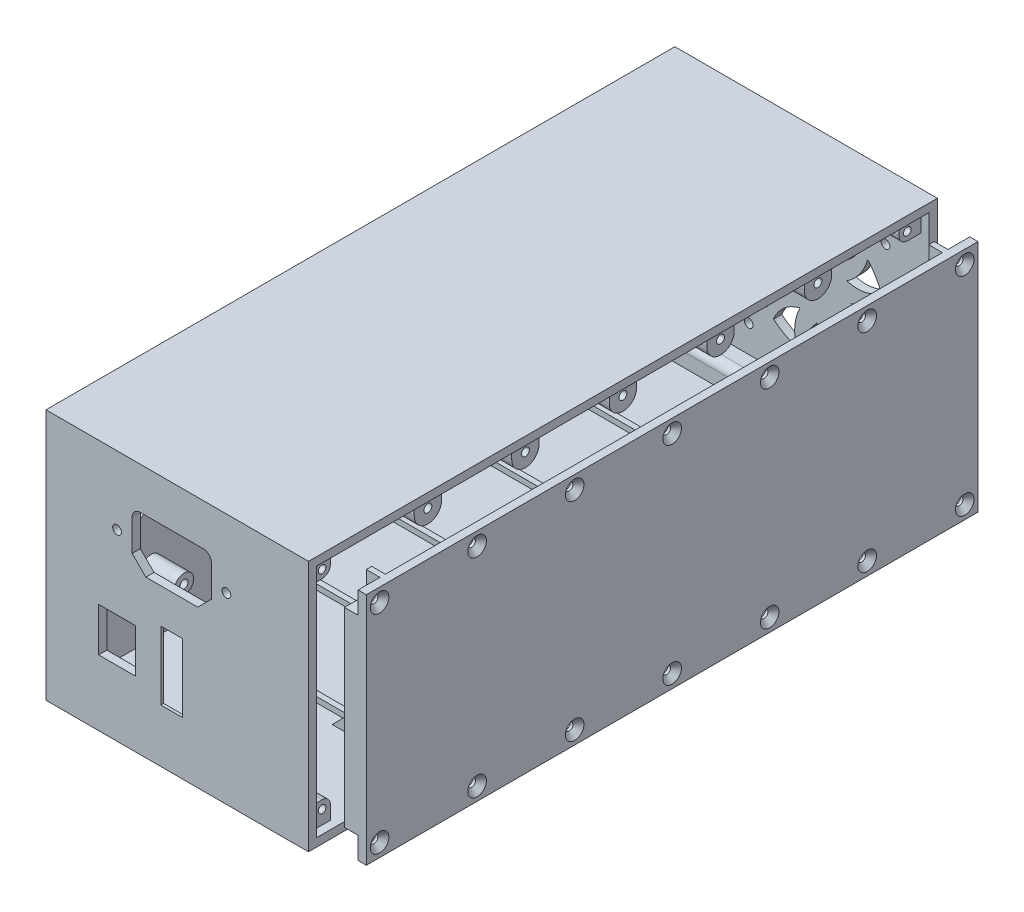
SolidWorks part; units mm, degrees
ref_plane "Front Plane" through (0, 0, 0) normal (0, 0, 1) x (1, 0, 0)
ref_plane "Top Plane" through (0, 0, 0) normal (0, 1, 0) x (1, 0, 0)
ref_plane "Right Plane" through (0, 0, 0) normal (1, 0, 0) x (0, 0, -1)
sketch "Sketch1" plane through (0, 0, 0) normal (1, 0, 0) x (0, 0, -1)
  line L1 (115, 46) -> (-115, 46)
  line L2 (115, 46) -> (115, -46)
  line L3 (115, -46) -> (-115, -46)
  line L4 (-115, 46) -> (-115, -46)
  line L5 (115, 46) -> (-115, -46) construction
  line L6 (115, -46) -> (-115, 46) construction
  point P0 (0, 0)
  dimension "D1" = 92
  dimension "D2" = 230
extrude "Boss-Extrude1" add sketch "Sketch1" along normal blind 3
sketch "Sketch2" plane through (3, 0, 0) normal (1, 0, 0) x (0, 0, -1)
  line L0 (-112, 43) -> (-112, -43)
  line L1 (-112, -43) -> (112, -43)
  line L2 (112, -43) -> (112, 43)
  line L3 (112, 43) -> (-112, 43)
  line L4 (-115, 46) -> (-115, -46)
  line L5 (-115, -46) -> (115, -46)
  line L6 (115, -46) -> (115, 46)
  line L7 (115, 46) -> (-115, 46)
  line L8 (-115, 46) -> (-115, -46)
  line L9 (-115, -46) -> (115, -46)
  line L10 (115, -46) -> (115, 46)
  line L11 (115, 46) -> (-115, 46)
  dimension "D1" = 0
  dimension "D2" = 3
extrude "Boss-Extrude2" add sketch "Sketch2" along normal blind 93
sketch "Sketch3" plane through (0, 0, 0) normal (-1, 0, 0) x (0, 0, 1)
  line L0 (-115, 0) -> (115, 0) construction
  line L1 (-115, -46) -> (-115, 46) construction
  line L2 (115, 46) -> (115, -46) construction
  line L3 (0, 46) -> (0, -46) construction
  line L4 (-115, 46) -> (115, 46) construction
  line L5 (115, -46) -> (-115, -46) construction
  line L6 (26.5, -7.75) -> (18.5, -7.75)
  line L7 (11.5, 7.75) -> (3.5, 7.75)
  line L8 (11.5, 7.75) -> (11.5, -7.75)
  line L9 (11.5, -7.75) -> (3.5, -7.75)
  line L10 (3.5, 7.75) -> (3.5, -7.75)
  line L11 (11.5, 7.75) -> (3.5, -7.75) construction
  line L12 (11.5, -7.75) -> (3.5, 7.75) construction
  line L13 (26.5, 7.75) -> (26.5, -7.75)
  line L14 (26.5, 7.75) -> (18.5, 7.75)
  line L15 (18.5, 7.75) -> (18.5, -7.75)
  line L16 (41.5, -7.75) -> (33.5, -7.75)
  line L17 (41.5, 7.75) -> (41.5, -7.75)
  line L18 (41.5, 7.75) -> (33.5, 7.75)
  line L19 (33.5, 7.75) -> (33.5, -7.75)
  line L20 (56.5, -7.75) -> (48.5, -7.75)
  line L21 (56.5, 7.75) -> (56.5, -7.75)
  line L22 (56.5, 7.75) -> (48.5, 7.75)
  line L23 (48.5, 7.75) -> (48.5, -7.75)
  line L24 (71.5, -7.75) -> (63.5, -7.75)
  line L25 (71.5, 7.75) -> (71.5, -7.75)
  line L26 (71.5, 7.75) -> (63.5, 7.75)
  line L27 (63.5, 7.75) -> (63.5, -7.75)
  line L28 (11.5, -7.75) -> (3.5, -7.75)
  line L29 (11.5, 7.75) -> (11.5, -7.75)
  line L30 (11.5, 7.75) -> (3.5, 7.75)
  line L31 (3.5, 7.75) -> (3.5, -7.75)
  line L32 (26.5, -7.75) -> (18.5, -7.75)
  line L33 (26.5, 7.75) -> (26.5, -7.75)
  line L34 (26.5, 7.75) -> (18.5, 7.75)
  line L35 (18.5, 7.75) -> (18.5, -7.75)
  line L36 (41.5, -7.75) -> (33.5, -7.75)
  line L37 (41.5, 7.75) -> (41.5, -7.75)
  line L38 (41.5, 7.75) -> (33.5, 7.75)
  line L39 (33.5, 7.75) -> (33.5, -7.75)
  line L40 (56.5, -7.75) -> (48.5, -7.75)
  line L41 (56.5, 7.75) -> (56.5, -7.75)
  line L42 (56.5, 7.75) -> (48.5, 7.75)
  line L43 (48.5, 7.75) -> (48.5, -7.75)
  line L44 (-3.5, -7.75) -> (-11.5, -7.75)
  line L45 (-3.5, 7.75) -> (-3.5, -7.75)
  line L46 (-3.5, 7.75) -> (-11.5, 7.75)
  line L47 (-11.5, 7.75) -> (-11.5, -7.75)
  line L48 (11.5, -7.75) -> (3.5, -7.75)
  line L49 (11.5, 7.75) -> (11.5, -7.75)
  line L50 (11.5, 7.75) -> (3.5, 7.75)
  line L51 (3.5, 7.75) -> (3.5, -7.75)
  line L52 (26.5, -7.75) -> (18.5, -7.75)
  line L53 (26.5, 7.75) -> (26.5, -7.75)
  line L54 (26.5, 7.75) -> (18.5, 7.75)
  line L55 (18.5, 7.75) -> (18.5, -7.75)
  line L56 (41.5, -7.75) -> (33.5, -7.75)
  line L57 (41.5, 7.75) -> (41.5, -7.75)
  line L58 (41.5, 7.75) -> (33.5, 7.75)
  line L59 (33.5, 7.75) -> (33.5, -7.75)
  line L60 (-18.5, -7.75) -> (-26.5, -7.75)
  line L61 (-18.5, 7.75) -> (-18.5, -7.75)
  line L62 (-18.5, 7.75) -> (-26.5, 7.75)
  line L63 (-26.5, 7.75) -> (-26.5, -7.75)
  line L64 (-3.5, -7.75) -> (-11.5, -7.75)
  line L65 (-3.5, 7.75) -> (-3.5, -7.75)
  line L66 (-3.5, 7.75) -> (-11.5, 7.75)
  line L67 (-11.5, 7.75) -> (-11.5, -7.75)
  line L68 (11.5, -7.75) -> (3.5, -7.75)
  line L69 (11.5, 7.75) -> (11.5, -7.75)
  line L70 (11.5, 7.75) -> (3.5, 7.75)
  line L71 (3.5, 7.75) -> (3.5, -7.75)
  line L72 (26.5, -7.75) -> (18.5, -7.75)
  line L73 (26.5, 7.75) -> (26.5, -7.75)
  line L74 (26.5, 7.75) -> (18.5, 7.75)
  line L75 (18.5, 7.75) -> (18.5, -7.75)
  line L76 (-33.5, -7.75) -> (-41.5, -7.75)
  line L77 (-33.5, 7.75) -> (-33.5, -7.75)
  line L78 (-33.5, 7.75) -> (-41.5, 7.75)
  line L79 (-41.5, 7.75) -> (-41.5, -7.75)
  line L80 (-18.5, -7.75) -> (-26.5, -7.75)
  line L81 (-18.5, 7.75) -> (-18.5, -7.75)
  line L82 (-18.5, 7.75) -> (-26.5, 7.75)
  line L83 (-26.5, 7.75) -> (-26.5, -7.75)
  line L84 (-3.5, -7.75) -> (-11.5, -7.75)
  line L85 (-3.5, 7.75) -> (-3.5, -7.75)
  line L86 (-3.5, 7.75) -> (-11.5, 7.75)
  line L87 (-11.5, 7.75) -> (-11.5, -7.75)
  line L88 (11.5, -7.75) -> (3.5, -7.75)
  line L89 (11.5, 7.75) -> (11.5, -7.75)
  line L90 (11.5, 7.75) -> (3.5, 7.75)
  line L91 (3.5, 7.75) -> (3.5, -7.75)
  line L92 (-48.5, -7.75) -> (-56.5, -7.75)
  line L93 (-48.5, 7.75) -> (-48.5, -7.75)
  line L94 (-48.5, 7.75) -> (-56.5, 7.75)
  line L95 (-56.5, 7.75) -> (-56.5, -7.75)
  line L96 (-33.5, -7.75) -> (-41.5, -7.75)
  line L97 (-33.5, 7.75) -> (-33.5, -7.75)
  line L98 (-33.5, 7.75) -> (-41.5, 7.75)
  line L99 (-41.5, 7.75) -> (-41.5, -7.75)
  line L100 (-18.5, -7.75) -> (-26.5, -7.75)
  line L101 (-18.5, 7.75) -> (-18.5, -7.75)
  line L102 (-18.5, 7.75) -> (-26.5, 7.75)
  line L103 (-26.5, 7.75) -> (-26.5, -7.75)
  line L104 (-3.5, -7.75) -> (-11.5, -7.75)
  line L105 (-3.5, 7.75) -> (-3.5, -7.75)
  line L106 (-3.5, 7.75) -> (-11.5, 7.75)
  line L107 (-11.5, 7.75) -> (-11.5, -7.75)
  line L108 (-3.5, -7.75) -> (-11.5, -7.75)
  line L109 (-3.5, 7.75) -> (-3.5, -7.75)
  line L110 (-3.5, 7.75) -> (-11.5, 7.75)
  line L111 (-11.5, 7.75) -> (-11.5, -7.75)
  line L112 (-18.5, -7.75) -> (-26.5, -7.75)
  line L113 (-18.5, 7.75) -> (-18.5, -7.75)
  line L114 (-18.5, 7.75) -> (-26.5, 7.75)
  line L115 (-26.5, 7.75) -> (-26.5, -7.75)
  line L116 (-33.5, -7.75) -> (-41.5, -7.75)
  line L117 (-33.5, 7.75) -> (-33.5, -7.75)
  line L118 (-33.5, 7.75) -> (-41.5, 7.75)
  line L119 (-41.5, 7.75) -> (-41.5, -7.75)
  line L120 (-48.5, -7.75) -> (-56.5, -7.75)
  line L121 (-48.5, 7.75) -> (-48.5, -7.75)
  line L122 (-48.5, 7.75) -> (-56.5, 7.75)
  line L123 (-56.5, 7.75) -> (-56.5, -7.75)
  line L124 (-63.5, -7.75) -> (-71.5, -7.75)
  line L125 (-63.5, 7.75) -> (-63.5, -7.75)
  line L126 (-63.5, 7.75) -> (-71.5, 7.75)
  line L127 (-71.5, 7.75) -> (-71.5, -7.75)
  circle A0 centre (84.6037, 0) radius 1
  point P12 (7.5, 0)
  dimension "D6" = 2
  dimension "D1" = 7.5
  dimension "D2" = 15.5
  dimension "D3" = 8
  dimension "D4" = 5
  dimension "D5" = 6
extrude "Cut-Extrude1" cut sketch "Sketch3" against normal up to surface (3 mm away) contours L126 L127 L124 L125 | L94 L95 L92 L93 | L78 L79 L76 L77 | L62 L63 L60 L61 | L46 L47 L44 L45 | L7 L10 L9 L8 | L14 L15 L6 L13 | L18 L19 L16 L17 | L22 L23 L20 L21 | L26 L27 L24 L25 | A0 region at (0, 0, 22.5) region at (0, 0, 7.5) region at (0, 0, 37.5) region at (0, 0, 52.5) region at (0, 0, 67.5) region at (0, 0, -7.5) region at (0, 0, -22.5) region at (0, 0, -37.5) region at (0, 0, -52.5) region at (0, 0, -67.5) region at (0, 0, 84.6037) up to face at (3, 0, 0)
sketch "Sketch4" plane through (96, 0, 0) normal (1, 0, 0) x (0, 0, -1)
  line L0 (0, 43) -> (0, -43) construction
  line L1 (112, 43) -> (-112, 43) construction
  line L2 (-112, -43) -> (112, -43) construction
  line L3 (-112, 43) -> (-112, -43) construction
  line L4 (-104, 38) -> (-104, 43)
  line L5 (-104, 43) -> (-112, 43)
  line L6 (-112, 43) -> (-112, 35)
  line L7 (-112, 35) -> (-107, 35)
  line L8 (0, 0) -> (-112, 0) construction
  line L9 (-107, -35) -> (-112, -35)
  line L10 (-112, 43) -> (-112, -43) construction
  line L11 (-112, -35) -> (-112, -43)
  line L12 (-104, -38) -> (-104, -43)
  line L13 (-104, -43) -> (-112, -43)
  line L14 (104, -43) -> (112, -43)
  line L15 (112, -35) -> (112, -43)
  line L16 (107, -35) -> (112, -35)
  line L17 (112, 35) -> (107, 35)
  line L18 (112, 43) -> (112, 35)
  line L19 (104, 43) -> (112, 43)
  line L20 (104, 38) -> (104, 43)
  line L21 (104, -38) -> (104, -43)
  circle A0 centre (-107, 38) radius 1.4
  circle A1 centre (-107, -38) radius 1.4
  arc A2 (-104, 38) -> (-107, 35) centre (-107, 38) cw
  arc A3 (-107, -35) -> (-104, -38) centre (-107, -38) cw
  arc A4 (107, -35) -> (104, -38) centre (107, -38) ccw
  circle A5 centre (107, -38) radius 1.4
  arc A6 (104, 38) -> (107, 35) centre (107, 38) ccw
  circle A7 centre (107, 38) radius 1.4
  dimension "D5" = 2.8
  dimension "D6" = 3
  dimension "D1" = 5
  dimension "D2" = 5
  dimension "D3" = 5
  dimension "D4" = 5
extrude "Boss-Extrude3" add sketch "Sketch4" against normal up to surface (93 mm away) from offset 3 up to face at (3, 0, -67.5) offset against normal yes
sketch "Sketch5" plane through (93, 0, 0) normal (1, 0, 0) x (0, 0, -1)
  circle A0 centre (-107, -38) radius 1.4 construction
  circle A1 centre (107, -38) radius 1.4 construction
  circle A2 centre (107, 38) radius 1.4 construction
  circle A3 centre (-107, 38) radius 1.4 construction
  circle A4 centre (-107, -38) radius 1.4
  circle A5 centre (107, -38) radius 1.4
  circle A6 centre (107, 38) radius 1.4
  circle A7 centre (-107, 38) radius 1.4
extrude "Boss-Extrude4" add sketch "Sketch5" against normal up to surface (90 mm away) from offset 20 up to face at (3, 0, -67.5) offset against normal yes
sketch "Sketch6" plane through (0, 0, 115) normal (0, 0, 1) x (1, 0, 0)
  line L0 (46, 46) -> (46, -46) construction
  line L1 (96, 46) -> (0, 46) construction
  line L2 (96, -46) -> (0, -46) construction
  line L3 (93, 43) -> (93, 38) construction
  line L4 (79.2275, 21) -> (12.7725, 21) construction
  line L5 (36.5, 11.25) -> (31.5, 16.25)
  line L6 (57.5, 30.75) -> (34.5, 30.75)
  line L7 (60.5, 27.75) -> (60.5, 16.25)
  line L8 (55.5, 11.25) -> (36.5, 11.25)
  line L9 (31.5, 27.75) -> (31.5, 16.25)
  line L10 (60.5, 30.75) -> (31.5, 11.25) construction
  line L11 (60.5, 11.25) -> (31.5, 30.75) construction
  line L12 (60.5, 16.25) -> (55.5, 11.25)
  line L14 (50, -1.5) -> (42, -1.5)
  line L15 (50, -1.5) -> (50, -26.5)
  line L16 (50, -26.5) -> (42, -26.5)
  line L17 (42, -1.5) -> (42, -26.5)
  line L18 (50, -1.5) -> (42, -26.5) construction
  line L19 (50, -26.5) -> (42, -1.5) construction
  line L20 (32.75, -6) -> (19.25, -6)
  line L21 (32.75, -6) -> (32.75, -22)
  line L22 (32.75, -22) -> (19.25, -22)
  line L23 (19.25, -6) -> (19.25, -22)
  line L24 (32.75, -6) -> (19.25, -22) construction
  line L25 (32.75, -22) -> (19.25, -6) construction
  circle A2 centre (26, 21) radius 1.6
  circle A3 centre (66, 21) radius 1.6
  arc A4 (57.5, 30.75) -> (60.5, 27.75) centre (57.5, 27.75) cw
  arc A5 (34.5, 30.75) -> (31.5, 27.75) centre (34.5, 27.75) ccw
  point P11 (46, 21)
  point P15 (46, 21)
  point P30 (46, -14)
  point P35 (26, -14)
  dimension "D2" = 3.2
  dimension "D7" = 3
  dimension "D1" = 47
  dimension "D3" = 20
  dimension "D4" = 20
  dimension "D5" = 29
  dimension "D6" = 19.5
  dimension "D8" = 25
  dimension "D9" = 8
  dimension "D10" = 25
  dimension "D13" = 32
  dimension "D14" = 20
  dimension "D15" = 13.5
  dimension "D16" = 16
extrude "Cut-Extrude2" cut sketch "Sketch6" against normal up to surface (3 mm away) up to face at (71.25, 0, 112)
sketch "Sketch7" plane through (0, 0, 112) normal (0, 0, -1) x (-1, 0, 0)
  line L0 (-39.5, 6) -> (-39.5, -32.5)
  line L1 (-39.5, -32.5) -> (-52, -32.5)
  line L2 (-52, -32.5) -> (-52, 6)
  line L3 (-52, 6) -> (-39.5, 6)
  line L4 (-50, -1.5) -> (-42, -1.5) construction
  line L5 (-50, -26.5) -> (-50, -1.5) construction
  dimension "D1" = 7.5
  dimension "D2" = 2
  dimension "D3" = 38.5
  dimension "D4" = 12.5
extrude "Cut-Extrude3" cut sketch "Sketch7" against normal blind 2
chamfer "Chamfer1" distance 2 angle 45 1 edges at (52, -13.25, 112)
sketch "Sketch8" plane through (3, 0, 0) normal (1, 0, 0) x (0, 0, -1)
  line L0 (-71.5, 0) -> (91.1958, 0) construction
  line L1 (-71.5, -7.75) -> (-71.5, 7.75) construction
  line L2 (-79.5, 43) -> (-79.5, -43) construction
  line L3 (112, 43) -> (-112, 43) construction
  line L4 (-104, -43) -> (104, -43) construction
  circle A0 centre (-79.5, 19.5) radius 1.5
  circle A1 centre (-79.5, -19.5) radius 1.5
  circle A2 centre (-79.5, 19.5) radius 3.5
  circle A3 centre (-79.5, -19.5) radius 3.5
  circle A4 centre (72, -19.5) radius 1.5
  circle A5 centre (72, -19.5) radius 3.5
  circle A6 centre (72, 19.5) radius 3.5
  circle A7 centre (72, 19.5) radius 1.5
  dimension "D1" = 3
  dimension "D2" = 7
  dimension "D3" = 8
  dimension "D5" = 19.5
  dimension "D6" = 19.5
  dimension "D7" = 19.5
  dimension "D8" = 19.5
  dimension "D9" = 151.5
extrude "Boss-Extrude5" add sketch "Sketch8" along normal blind 12
sketch "Sketch9" plane through (3, 0, 0) normal (1, 0, 0) x (0, 0, -1)
  circle A0 centre (-84.6037, 0) radius 3
extrude "Cut-Extrude4" cut sketch "Sketch9" against normal blind 2.2
ref_plane "Plane1" through (106, 0, 0) normal (1, 0, 0) x (0, 0, -1)
sketch "Sketch10" plane through (106, 0, 0) normal (1, 0, 0) x (0, 0, -1)
  line L112 (107, -32.85) -> (109.85, -32.85)
  line L113 (109.85, -32.85) -> (109.85, 32.85)
  line L114 (109.85, 32.85) -> (107, 32.85)
  line L115 (101.85, 38) -> (101.85, 40.85)
  line L116 (101.85, 40.85) -> (-101.85, 40.85)
  line L117 (-101.85, 40.85) -> (-101.85, 38)
  line L118 (-107, 32.85) -> (-109.85, 32.85)
  line L119 (-109.85, 32.85) -> (-109.85, -32.85)
  line L120 (-109.85, -32.85) -> (-107, -32.85)
  line L121 (-101.85, -38) -> (-101.85, -40.85)
  line L122 (-101.85, -40.85) -> (101.85, -40.85)
  line L123 (101.85, -40.85) -> (101.85, -38)
  line L124 (107, -34.85) -> (111.85, -34.85)
  line L125 (103.85, -42.85) -> (103.85, -38)
  line L126 (-103.85, -42.85) -> (103.85, -42.85)
  line L127 (-103.85, -38) -> (-103.85, -42.85)
  line L128 (-111.85, -34.85) -> (-107, -34.85)
  line L129 (-111.85, 34.85) -> (-111.85, -34.85)
  line L130 (-107, 34.85) -> (-111.85, 34.85)
  line L131 (-103.85, 42.85) -> (-103.85, 38)
  line L132 (103.85, 42.85) -> (-103.85, 42.85)
  line L133 (103.85, 38) -> (103.85, 42.85)
  line L134 (111.85, 34.85) -> (107, 34.85)
  line L135 (111.85, -34.85) -> (111.85, 34.85)
  line L136 (107, -34.85) -> (111.85, -34.85)
  line L137 (103.85, -42.85) -> (103.85, -38)
  line L138 (-103.85, -42.85) -> (103.85, -42.85)
  line L139 (-103.85, -38) -> (-103.85, -42.85)
  line L140 (-111.85, -34.85) -> (-107, -34.85)
  line L141 (-111.85, 34.85) -> (-111.85, -34.85)
  line L142 (-107, 34.85) -> (-111.85, 34.85)
  line L143 (-103.85, 42.85) -> (-103.85, 38)
  line L144 (103.85, 42.85) -> (-103.85, 42.85)
  line L145 (103.85, 38) -> (103.85, 42.85)
  line L146 (111.85, 34.85) -> (107, 34.85)
  line L147 (111.85, -34.85) -> (111.85, 34.85)
  arc A36 (107, -34.85) -> (103.85, -38) centre (107, -38) ccw
  arc A37 (-103.85, -38) -> (-107, -34.85) centre (-107, -38) ccw
  arc A38 (-107, 34.85) -> (-103.85, 38) centre (-107, 38) ccw
  arc A39 (103.85, 38) -> (107, 34.85) centre (107, 38) ccw
  arc A40 (107, -34.85) -> (103.85, -38) centre (107, -38) ccw
  arc A41 (-103.85, -38) -> (-107, -34.85) centre (-107, -38) ccw
  arc A42 (-107, 34.85) -> (-103.85, 38) centre (-107, 38) ccw
  arc A43 (103.85, 38) -> (107, 34.85) centre (107, 38) ccw
  arc A48 (101.85, 38) -> (107, 32.85) centre (107, 38) ccw
  arc A49 (-107, 32.85) -> (-101.85, 38) centre (-107, 38) ccw
  arc A50 (-101.85, -38) -> (-107, -32.85) centre (-107, -38) ccw
  arc A51 (107, -32.85) -> (101.85, -38) centre (107, -38) ccw
  dimension "D1" = 0.15
  dimension "D2" = 2
extrude "Boss-Extrude6" add sketch "Sketch10" along normal blind 5 separate body
sketch "Sketch11" plane through (111, 0, 0) normal (1, 0, 0) x (0, 0, -1)
  line L0 (111.85, -34.85) -> (111.85, 34.85) construction
  line L1 (-103.85, -42.85) -> (103.85, -42.85) construction
  line L2 (-111.85, 34.85) -> (-111.85, -34.85) construction
  line L3 (103.85, 42.85) -> (-103.85, 42.85) construction
  line L4 (111.85, -34.85) -> (111.85, 34.85)
  line L5 (-103.85, -42.85) -> (103.85, -42.85)
  line L6 (-111.85, 34.85) -> (-111.85, -34.85)
  line L7 (103.85, 42.85) -> (-103.85, 42.85)
  line L8 (103.85, 42.85) -> (111.85, 42.85)
  line L9 (111.85, 42.85) -> (111.85, 34.85)
  line L10 (111.85, -34.85) -> (111.85, -42.85)
  line L11 (111.85, -42.85) -> (103.85, -42.85)
  line L12 (-111.85, -34.85) -> (-111.85, -42.85)
  line L13 (-111.85, -42.85) -> (-103.85, -42.85)
  line L14 (-103.85, 42.85) -> (-111.85, 42.85)
  line L15 (-111.85, 42.85) -> (-111.85, 34.85)
  circle A0 centre (-107, -38) radius 1.4 construction
  circle A1 centre (107, -38) radius 1.4 construction
  circle A2 centre (107, 38) radius 1.4 construction
  circle A3 centre (-107, 38) radius 1.4 construction
  circle A4 centre (-107, -38) radius 1.4
  circle A5 centre (107, -38) radius 1.4
  circle A6 centre (107, 38) radius 1.4
  circle A7 centre (-107, 38) radius 1.4
extrude "Boss-Extrude7" add sketch "Sketch11" along normal blind 3
sketch "Sketch12" plane through (114, 0, 0) normal (1, 0, 0) x (0, 0, -1)
  line L0 (-112, 0) -> (111.85, 0) construction
  line L1 (89, 29.25) -> (-89, 29.25) construction
  line L2 (89, 29.25) -> (89, -29.25) construction
  line L3 (89, -29.25) -> (-89, -29.25) construction
  line L4 (-89, 29.25) -> (-89, -29.25) construction
  line L5 (89, 29.25) -> (-89, -29.25) construction
  line L6 (89, -29.25) -> (-89, 29.25) construction
  line L7 (-112, 43) -> (-112, -43) construction
  line L8 (111.85, -42.85) -> (111.85, 42.85) construction
  circle A0 centre (-89, 29.25) radius 1.8
  circle A1 centre (-89, -29.25) radius 1.8
  circle A2 centre (89, -29.25) radius 1.8
  circle A3 centre (89, 29.25) radius 1.8
  circle A4 centre (-47.3819, 9) radius 1.8
  circle A5 centre (26.6181, 9) radius 1.8
  circle A6 centre (-4.3819, 9) radius 1.8
  circle A7 centre (-4.3819, -9) radius 1.8
  point P0 (0, 0)
  dimension "D3" = 3.6
  dimension "D10" = 3.6
  dimension "D1" = 58.5
  dimension "D2" = 178
  dimension "D4" = 9
  dimension "D5" = 9
  dimension "D6" = 74
  dimension "D7" = 31
  dimension "D8" = 9
  dimension "D9" = 9
sketch "Sketch13" plane through (96, 0, 0) normal (1, 0, 0) x (0, 0, -1)
  line L12 (104, 38) -> (104, 43)
  line L13 (104, 43) -> (-104, 43)
  line L14 (-104, 43) -> (-104, 38)
  line L15 (-107, 35) -> (-112, 35)
  line L16 (-112, 35) -> (-112, -35)
  line L17 (-112, -35) -> (-107, -35)
  line L18 (-104, -38) -> (-104, -43)
  line L19 (-104, -43) -> (104, -43)
  line L20 (104, -43) -> (104, -38)
  line L21 (107, -35) -> (112, -35)
  line L22 (112, -35) -> (112, 35)
  line L23 (112, 35) -> (107, 35)
  line L24 (104, 38) -> (104, 43)
  line L25 (104, 43) -> (-104, 43)
  line L26 (-104, 43) -> (-104, 38)
  line L27 (-107, 35) -> (-112, 35)
  line L28 (-112, 35) -> (-112, -35)
  line L29 (-112, -35) -> (-107, -35)
  line L30 (-104, -38) -> (-104, -43)
  line L31 (-104, -43) -> (104, -43)
  line L32 (104, -43) -> (104, -38)
  line L33 (107, -35) -> (112, -35)
  line L34 (112, -35) -> (112, 35)
  line L35 (112, 35) -> (107, 35)
  arc A4 (104, 38) -> (107, 35) centre (107, 38) ccw
  arc A5 (-107, 35) -> (-104, 38) centre (-107, 38) ccw
  arc A6 (-104, -38) -> (-107, -35) centre (-107, -38) ccw
  arc A7 (107, -35) -> (104, -38) centre (107, -38) ccw
  arc A8 (104, 38) -> (107, 35) centre (107, 38) ccw
  arc A9 (-107, 35) -> (-104, 38) centre (-107, 38) ccw
  arc A10 (-104, -38) -> (-107, -35) centre (-107, -38) ccw
  arc A11 (107, -35) -> (104, -38) centre (107, -38) ccw
  dimension "D1" = 0
sketch "Sketch14" plane through (93, 0, 0) normal (1, 0, 0) x (0, 0, -1)
  line L0 (-68.334, -43) -> (-68.334, -41)
  line L2 (-104, -43) -> (-104, -38) construction
  line L3 (-68.334, 43) -> (-68.334, 41)
  line L5 (-104, 38) -> (-104, 43) construction
  dimension "D1" = 35.666
  dimension "D2" = 35.666
extrude "Extrude-Thin2" add sketch "Sketch14" against normal up to surface (90 mm away) from offset 3 thin up to face at (3, 0, 81.6037) offset against normal yes thin type mid plane wall 2
pattern_linear "LPattern1" count 5 spacing 35.666 along (0, 0, -1) of "Extrude-Thin2"
sketch "Sketch15" plane through (3, 40, 0) normal (1, 0, 0) x (0, 1, 0)
  line L0 (-40, 112) -> (-40, -112.6115) construction
  line L2 (-5, 112) -> (-75, 112) construction
  line L3 (-13.5, 36.1943) -> (-66.5, 36.1943) construction
  line L4 (-13.5, 36.1943) -> (-13.5, -36.8057) construction
  line L5 (-13.5, -36.8057) -> (-66.5, -36.8057) construction
  line L6 (-66.5, 36.1943) -> (-66.5, -36.8057) construction
  line L7 (-13.5, 36.1943) -> (-66.5, -36.8057) construction
  line L8 (-13.5, -36.8057) -> (-66.5, 36.1943) construction
  circle A0 centre (-13.5, 36.1943) radius 1.25
  circle A1 centre (-66.5, 36.1943) radius 1.25
  circle A2 centre (-66.5, -36.8057) radius 1.25
  circle A4 centre (-66.5, 36.1943) radius 2.5
  circle A5 centre (-13.5, 36.1943) radius 2.5
  circle A7 centre (-66.5, -36.8057) radius 2.5
  circle A8 centre (-13.5, -36.8057) radius 1.25
  circle A9 centre (-13.5, -36.8057) radius 2.5
  point P4 (-40, -0.3057)
  point P20 (-40, 112)
  dimension "D3" = 2.5
  dimension "D4" = 5
  dimension "D1" = 53
  dimension "D2" = 73
extrude "Boss-Extrude9" add sketch "Sketch15" along normal blind 20
sketch "Sketch16" plane through (0, 0, -112) normal (0, 0, 1) x (1, 0, 0)
  line L0 (3, 0) -> (96, 0) construction
  line L1 (3, -35) -> (3, 35) construction
  line L3 (55, 0) -> (67.5, 0) construction
  line L4 (80, 25) -> (30, 25) construction
  line L5 (80, 25) -> (80, -25) construction
  line L6 (80, -25) -> (30, -25) construction
  line L7 (30, 25) -> (30, -25) construction
  line L8 (80, 25) -> (30, -25) construction
  line L9 (80, -25) -> (30, 25) construction
  line L10 (55, 0) -> (65.8253, -6.25) construction
  line L11 (96, -35) -> (96, 35) construction
  circle A0 centre (30, 25) radius 1.6
  circle A1 centre (80, 25) radius 1.6
  circle A2 centre (80, -25) radius 1.6
  circle A3 centre (30, -25) radius 1.6
  circle A4 centre (55, 0) radius 12.5 construction
  arc A5 (79.4256, 5.3285) -> (79.6515, -4.1595) centre (55, 0) cw
  arc A6 (78.8174, -7.5982) -> (74.2691, -15.928) centre (55, 0) cw
  arc A7 (71.8274, -18.4889) -> (63.7236, -23.4286) centre (55, 0) cw
  arc A8 (60.3285, -24.4256) -> (50.8405, -24.6515) centre (55, 0) cw
  arc A9 (47.4018, -23.8174) -> (39.072, -19.2691) centre (55, 0) cw
  arc A10 (36.5111, -16.8274) -> (31.5714, -8.7236) centre (55, 0) cw
  arc A11 (30.5744, -5.3285) -> (30.3485, 4.1595) centre (55, 0) cw
  arc A12 (31.1826, 7.5982) -> (35.7309, 15.928) centre (55, 0) cw
  arc A13 (38.1726, 18.4889) -> (46.2764, 23.4286) centre (55, 0) cw
  arc A14 (49.6715, 24.4256) -> (59.1595, 24.6515) centre (55, 0) cw
  arc A15 (62.5982, 23.8174) -> (70.928, 19.2691) centre (55, 0) cw
  arc A16 (73.4889, 16.8274) -> (78.4286, 8.7236) centre (55, 0) cw
  spline S0 degree 2 poles (79.4256, 5.3285) (74.5238, 0.5174) (67.5, 0) knots 0 0 0 1 1 1
  spline S1 degree 2 poles (67.5, 0) (72.6575, -5.0815) (79.6515, -4.1595) knots 0 0 0 1 1 1
  spline S2 degree 2 poles (78.8174, -7.5982) (72.1668, -9.3138) (65.8253, -6.25) knots 0 0 0 1 1 1
  spline S3 degree 2 poles (65.8253, -6.25) (67.7511, -13.2294) (74.2691, -15.928) knots 0 0 0 1 1 1
  spline S4 degree 2 poles (71.8274, -18.4889) (65.21, -16.6494) (61.25, -10.8253) knots 0 0 0 1 1 1
  spline S5 degree 2 poles (61.25, -10.8253) (59.428, -17.8326) (63.7236, -23.4286) knots 0 0 0 1 1 1
  spline S6 degree 2 poles (60.3285, -24.4256) (55.5174, -19.5238) (55, -12.5) knots 0 0 0 1 1 1
  spline S7 degree 2 poles (55, -12.5) (49.9185, -17.6575) (50.8405, -24.6515) knots 0 0 0 1 1 1
  spline S8 degree 2 poles (47.4018, -23.8174) (45.6862, -17.1668) (48.75, -10.8253) knots 0 0 0 1 1 1
  spline S9 degree 2 poles (48.75, -10.8253) (41.7706, -12.7511) (39.072, -19.2691) knots 0 0 0 1 1 1
  spline S10 degree 2 poles (36.5111, -16.8274) (38.3506, -10.21) (44.1747, -6.25) knots 0 0 0 1 1 1
  spline S11 degree 2 poles (44.1747, -6.25) (37.1674, -4.428) (31.5714, -8.7236) knots 0 0 0 1 1 1
  spline S12 degree 2 poles (30.5744, -5.3285) (35.4762, -0.5174) (42.5, 0) knots 0 0 0 1 1 1
  spline S13 degree 2 poles (42.5, 0) (37.3425, 5.0815) (30.3485, 4.1595) knots 0 0 0 1 1 1
  spline S14 degree 2 poles (31.1826, 7.5982) (37.8332, 9.3138) (44.1747, 6.25) knots 0 0 0 1 1 1
  spline S15 degree 2 poles (44.1747, 6.25) (42.2489, 13.2294) (35.7309, 15.928) knots 0 0 0 1 1 1
  spline S16 degree 2 poles (38.1726, 18.4889) (44.79, 16.6494) (48.75, 10.8253) knots 0 0 0 1 1 1
  spline S17 degree 2 poles (48.75, 10.8253) (50.572, 17.8326) (46.2764, 23.4286) knots 0 0 0 1 1 1
  spline S18 degree 2 poles (49.6715, 24.4256) (54.4826, 19.5238) (55, 12.5) knots 0 0 0 1 1 1
  spline S19 degree 2 poles (55, 12.5) (60.0815, 17.6575) (59.1595, 24.6515) knots 0 0 0 1 1 1
  spline S20 degree 2 poles (62.5982, 23.8174) (64.3138, 17.1668) (61.25, 10.8253) knots 0 0 0 1 1 1
  spline S21 degree 2 poles (61.25, 10.8253) (68.2294, 12.7511) (70.928, 19.2691) knots 0 0 0 1 1 1
  spline S22 degree 2 poles (73.4889, 16.8274) (71.6494, 10.21) (65.8253, 6.25) knots 0 0 0 1 1 1
  spline S23 degree 2 poles (65.8253, 6.25) (72.8326, 4.428) (78.4286, 8.7236) knots 0 0 0 1 1 1
  point P6 (55, 0)
  point P83 (96, 0)
  dimension "D4" = 3.2
  dimension "D5" = 25
  dimension "D6" = 12
  dimension "D1" = 50
  dimension "D2" = 50
  dimension "D7" = 30
extrude "Cut-Extrude6" cut sketch "Sketch16" against normal up to surface (3 mm away) up to face at (48, 0, -115)
sketch "Sketch17" plane through (111, 0, 0) normal (-1, 0, 0) x (0, 0, 1)
  line L0 (-109.85, -0.85) -> (109.85, -0.85) construction
  line L1 (-109.85, -32.85) -> (-109.85, 32.85) construction
  line L2 (109.85, 32.85) -> (109.85, -32.85) construction
  line L3 (101.85, -40.85) -> (-101.85, -40.85) construction
  line L4 (-8.5, 20.1) -> (-91.2, 20.1) construction
  line L5 (-8.5, 20.1) -> (-8.5, -21.8) construction
  line L6 (-8.5, -21.8) -> (-91.2, -21.8) construction
  line L7 (-91.2, 20.1) -> (-91.2, -21.8) construction
  line L8 (-8.5, 20.1) -> (-91.2, -21.8) construction
  line L9 (-8.5, -21.8) -> (-91.2, 20.1) construction
  line L10 (79.15, 12.15) -> (21.15, 12.15) construction
  line L11 (79.15, 12.15) -> (79.15, -13.85) construction
  line L12 (79.15, -13.85) -> (21.15, -13.85) construction
  line L13 (21.15, 12.15) -> (21.15, -13.85) construction
  line L14 (79.15, 12.15) -> (21.15, -13.85) construction
  line L15 (79.15, -13.85) -> (21.15, 12.15) construction
  line L16 (-109.85, -32.85) -> (-109.85, 32.85) construction
  circle A0 centre (-91.2, 20.1) radius 1.4
  circle A1 centre (-91.2, -21.8) radius 1.4
  circle A2 centre (-8.5, -21.8) radius 1.4
  circle A3 centre (-8.5, 20.1) radius 1.4
  circle A4 centre (79.15, 12.15) radius 1.4
  circle A5 centre (21.15, 12.15) radius 1.4
  circle A6 centre (21.15, -13.85) radius 1.4
  circle A7 centre (79.15, -13.85) radius 1.4
  circle A8 centre (-91.2, 20.1) radius 3.25
  circle A9 centre (-8.5, 20.1) radius 3.25
  circle A10 centre (-8.5, -21.8) radius 3.25
  circle A11 centre (-91.2, -21.8) radius 3.25
  circle A12 centre (21.15, -13.85) radius 3.25
  circle A13 centre (21.15, 12.15) radius 3.25
  circle A14 centre (79.15, 12.15) radius 3.25
  circle A15 centre (79.15, -13.85) radius 3.25
  point P6 (-49.85, -0.85)
  point P11 (50.15, -0.85)
  dimension "D8" = 2.8
  dimension "D9" = 6.5
  dimension "D1" = 82.7
  dimension "D2" = 41.9
  dimension "D3" = 40
  dimension "D4" = 60
  dimension "D5" = 58
  dimension "D6" = 26
  dimension "D7" = 100
extrude "Boss-Extrude10" add sketch "Sketch17" along normal blind 5
sketch "Sketch18" plane through (93, 0, 0) normal (1, 0, 0) x (0, 0, -1)
  line L0 (74.33, -41) -> (74.33, -35.3123) construction
  line L1 (73.33, -41) -> (75.33, -41) construction
  line L2 (-112, -43) -> (112, -43) construction
  line L3 (69.33, -38) -> (69.33, -43)
  line L5 (69.33, -43) -> (79.33, -43)
  line L6 (79.33, -43) -> (79.33, -38)
  circle A0 centre (74.33, -38) radius 1.45
  arc A1 (69.33, -38) -> (79.33, -38) centre (74.33, -38) cw
  dimension "D1" = 2.9
  dimension "D3" = 5
  dimension "D2" = 5
extrude "Boss-Extrude11" add sketch "Sketch18" against normal blind 20
chamfer "Chamfer3" distance 10 angle 45 1 edges at (73, -43, -71.33)
ref_plane "Plane2" through (0, 0, 0) normal (0, -1, 0) x (-1, 0, 0)
mirror "Mirror4" about plane through (0, 0, 0) normal (0, -1, 0) of "Boss-Extrude11"
chamfer "Chamfer4" distance 10 angle 45 1 edges at (73, 43, -71.33)
pattern_linear "LPattern4" count 5 spacing 35.666 along (0, 0, 1) of "Boss-Extrude11", "Chamfer3", "Mirror4", "Chamfer4"
sketch "Sketch21" plane through (106, 0, 0) normal (-1, 0, 0) x (0, 0, 1)
  line L0 (-101.85, -44.15) -> (-101.85, -36.4687)
  line L1 (-101.85, 40.85) -> (101.8627, 40.85)
  line L2 (-101.85, 40.85) -> (-101.85, 48.5313)
  line L3 (-101.85, 48.5313) -> (101.8627, 48.5313)
  line L4 (101.8627, 40.85) -> (101.8627, 48.5313)
  line L5 (-101.85, -44.15) -> (101.8627, -44.15)
  line L6 (101.8627, -44.15) -> (101.8627, -36.4687)
  line L7 (-101.85, -36.4687) -> (101.8627, -36.4687)
  dimension "D1" = 2
extrude "Cut-Extrude7" cut sketch "Sketch21" against normal up to surface (5 mm away) up to face at (111, -13.85, 82.4)
sketch "Sketch22" plane through (114, 0, 0) normal (1, 0, 0) x (0, 0, -1)
  line L0 (-107, 38) -> (-71.334, 38) construction
  line L1 (-111.85, 0) -> (111.85, 0) construction
  line L2 (-111.85, 42.85) -> (-111.85, -42.85) construction
  line L3 (111.85, -42.85) -> (111.85, 42.85) construction
  circle A0 centre (-71.334, 38) radius 1.4
  circle A1 centre (-107, 38) radius 1.4 construction
  circle A2 centre (-35.668, 38) radius 1.4
  circle A3 centre (-0.002, 38) radius 1.4
  circle A4 centre (35.664, 38) radius 1.4
  circle A5 centre (71.33, 38) radius 1.4
  circle A6 centre (71.33, -38) radius 1.4
  circle A7 centre (35.664, -38) radius 1.4
  circle A8 centre (-0.002, -38) radius 1.4
  circle A9 centre (-35.668, -38) radius 1.4
  circle A10 centre (-71.334, -38) radius 1.4
  dimension "D2" = 35.666
  dimension "D3" = 35.666
  dimension "D1" = 5
extrude "Cut-Extrude8" cut sketch "Sketch22" against normal up to surface (3 mm away) up to face at (111, 4.5559, 11.3264)
chamfer "Chamfer5" distance 2 angle 45 14 edges at (114, -38, 105.6) (114, -38, 72.734) (114, -38, 37.068) (114, -38, 1.402) (114, -38, -34.264) (114, -38, -69.93) (114, -38, -108.4) (114, 38, -37.064) (114, 38, -1.398) (114, 38, 34.268) (114, 38, 105.6) (114, 38, 69.934) (114, 38, -108.4) (114, 38, -72.73)
